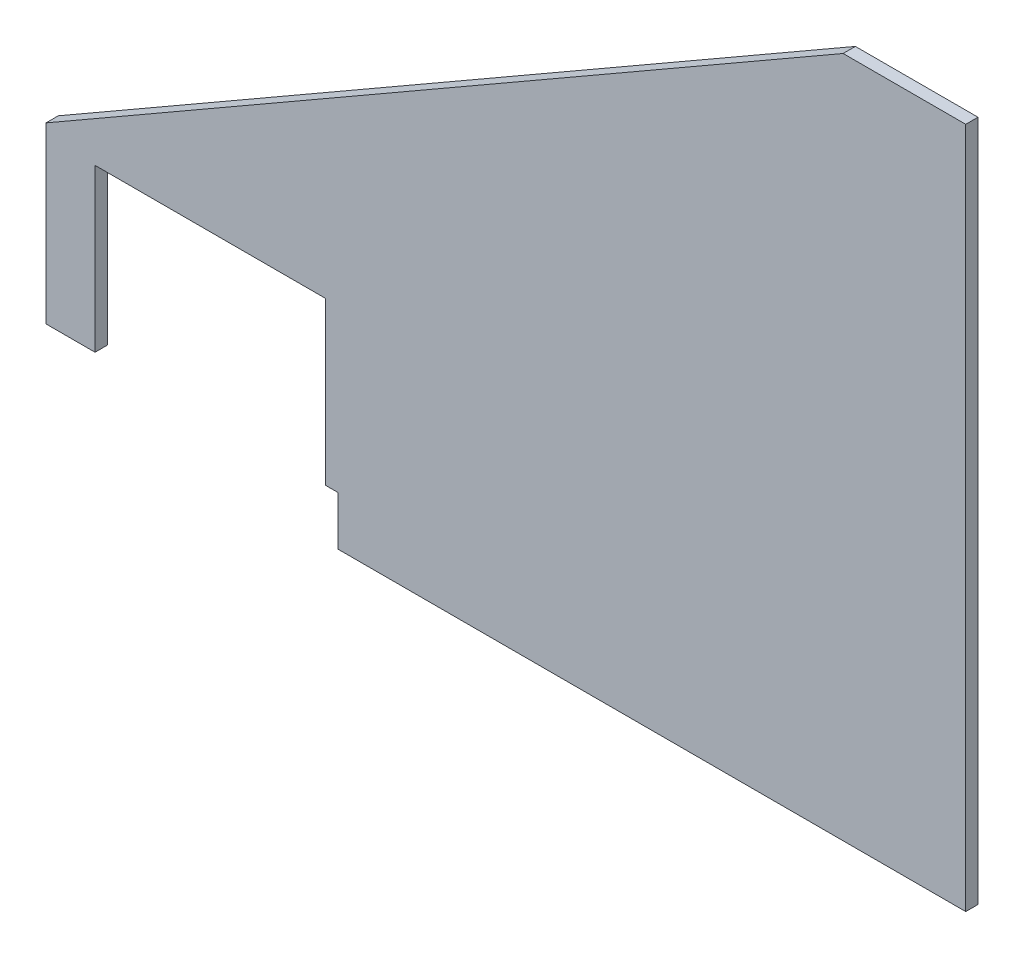
SolidWorks part; units mm, degrees
material "아크릴(내충격성)"
ref_plane "정면" through (0, 0, 0) normal (0, 0, 1) x (1, 0, 0)
ref_plane "윗면" through (0, 0, 0) normal (0, 1, 0) x (1, 0, 0)
ref_plane "우측면" through (0, 0, 0) normal (1, 0, 0) x (0, 0, -1)
sketch "스케치1" plane through (0, 0, 0) normal (0, 0, 1) x (1, 0, 0)
  line L0 (-128, -139) -> (128, -139)
  line L1 (128, -139) -> (128, 139)
  line L2 (128, 139) -> (78, 139)
  line L3 (78, 139) -> (-247, -48)
  line L7 (-128, -139) -> (-128, -119)
  line L8 (-133, -53) -> (-227, -53)
  line L11 (-247, -48) -> (-247, -119)
  line L12 (-247, -119) -> (-227, -119)
  line L13 (-227, -53) -> (-227, -119)
  line L14 (-128, -119) -> (-133, -119)
  line L17 (-133, -119) -> (-133, -53)
  point P3 (128, 0)
  point P6 (0, -139)
  dimension "D1" = 278
  dimension "D2" = 91
  dimension "D3" = 375
  dimension "D4" = 50
  dimension "D5" = 256
  dimension "D6" = 20
  dimension "D7" = 71
  dimension "D8" = 5
  dimension "D9" = 86
extrude "보스-돌출1" add sketch "스케치1" along normal blind 5 contours L3 L11 L12 L13 L8 L17 L14 L7 L0 L1 L2
